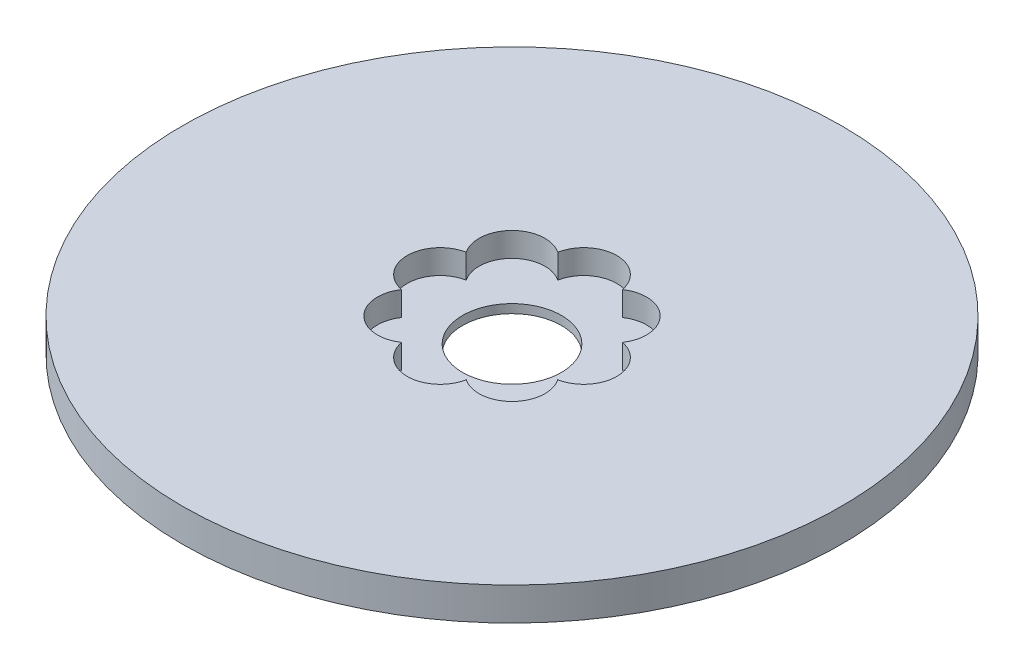
SolidWorks part; units mm, degrees
ref_plane "Front Plane" through (0, 0, 0) normal (0, 0, 1) x (1, 0, 0)
ref_plane "Top Plane" through (0, 0, 0) normal (0, 1, 0) x (1, 0, 0)
ref_plane "Right Plane" through (0, 0, 0) normal (1, 0, 0) x (0, 0, -1)
sketch "Sketch1" plane through (0, 0, 0) normal (0, 1, 0) x (1, 0, 0)
  circle A0 centre (0, 0) radius 100
  dimension "FLANGE_OD" = 200
extrude "Boss-Extrude1" add sketch "Sketch1" along normal blind 10
sketch "Sketch2" plane through (0, 0, 0) normal (0, 1, 0) x (1, 0, 0)
  circle A0 centre (0, 0) radius 15
  dimension "BORE_D" = 30
extrude "Cut-Extrude1" cut sketch "Sketch2" along normal through all
sketch "Sketch3" plane through (0, 10, 0) normal (0, 1, 0) x (1, 0, 0)
  circle A0 centre (0, 0) radius 21.7931 construction
  circle A1 centre (-21.7931, 0) radius 10
  dimension "BOLT_D" = 20
  dimension "BOLT_PCD" = 43.5861
extrude "Cut-Extrude2" cut sketch "Sketch3" against normal blind 7.3427
pattern_circular "CirPattern1" count 8 over 360 about axis through (0, 0, 0) along (0, 1, 0) of "Cut-Extrude2"
